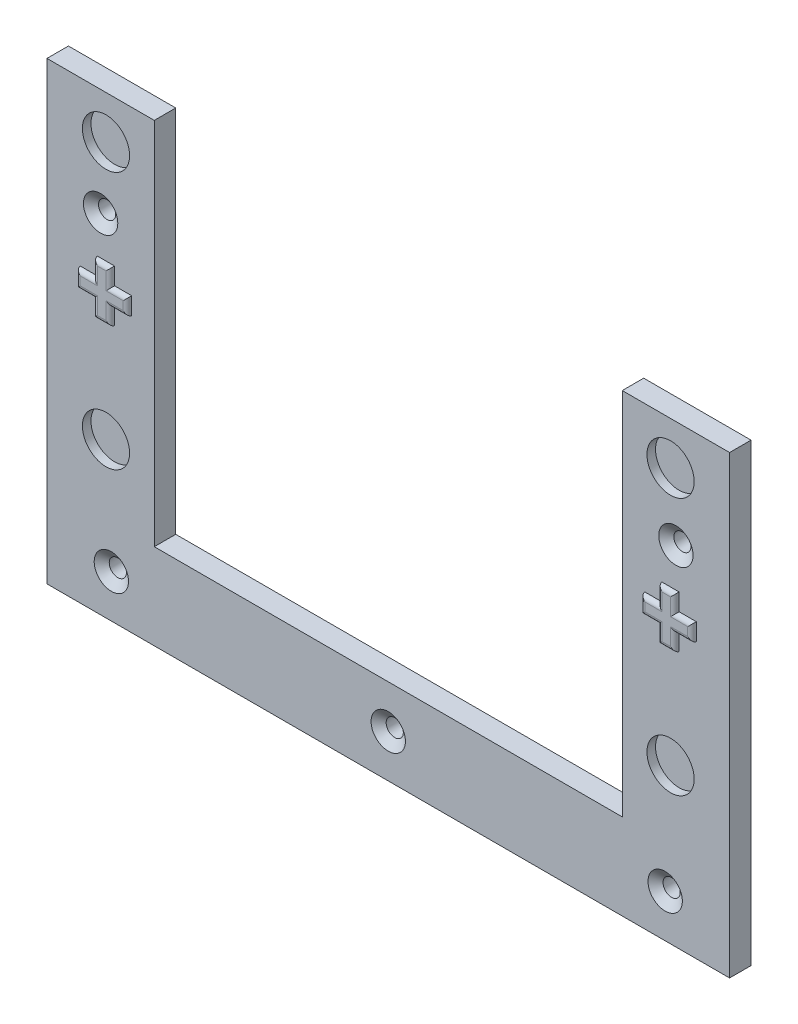
SolidWorks part; units mm, degrees
ref_plane "Plan de face" through (0, 0, 0) normal (0, 0, 1) x (1, 0, 0)
ref_plane "Plan de dessus" through (0, 0, 0) normal (0, 1, 0) x (1, 0, 0)
ref_plane "Plan de droite" through (0, 0, 0) normal (1, 0, 0) x (0, 0, -1)
sketch "Esquisse1" plane through (0, 0, 0) normal (0, 0, 1) x (1, 0, 0)
  line L1 (0, 0) -> (159, 0)
  line L2 (0, 0) -> (0, 106)
  line L3 (0, 106) -> (159, 106)
  line L4 (159, 0) -> (159, 106)
  dimension "D1" = 159
  dimension "D2" = 106
extrude "Boss.-Extru.1" add sketch "Esquisse1" along normal blind 5
sketch "Esquisse2" plane through (0, 0, 0) normal (0, 0, -1) x (-1, 0, 0)
  line L0 (-11.75, 64) -> (-7.75, 64)
  line L1 (-7.75, 64) -> (-7.75, 68)
  line L2 (-19.75, 64) -> (-19.75, 68)
  line L3 (-7.75, 68) -> (-11.75, 68)
  line L4 (-143.25, 64) -> (-139.25, 64)
  line L5 (-79.5, 174.4354) -> (-79.5, -40.1682) construction
  line L6 (-143.25, 68) -> (-139.25, 68)
  line L7 (-143.25, 60) -> (-143.25, 64)
  line L8 (-147.25, 60) -> (-143.25, 60)
  line L9 (-147.25, 64) -> (-147.25, 60)
  line L10 (-143.25, 72) -> (-143.25, 68)
  line L11 (-147.25, 72) -> (-143.25, 72)
  line L12 (-11.75, 68) -> (-11.75, 72)
  line L13 (-11.75, 72) -> (-15.75, 72)
  line L14 (-15.75, 72) -> (-15.75, 68)
  line L15 (-11.75, 64) -> (-11.75, 60)
  line L16 (-11.75, 60) -> (-15.75, 60)
  line L17 (-15.75, 60) -> (-15.75, 64)
  line L18 (-15.75, 68) -> (-19.75, 68)
  line L19 (-15.75, 64) -> (-19.75, 64)
  line L20 (0, 106) -> (0, 0) construction
  line L21 (-159, 0) -> (-159, 106) construction
  line L22 (-147.25, 68) -> (-147.25, 72)
  line L23 (-151.25, 68) -> (-147.25, 68)
  line L24 (-139.25, 64) -> (-139.25, 68)
  line L25 (-151.25, 64) -> (-151.25, 68)
  line L26 (-147.25, 64) -> (-151.25, 64)
  line L28 (-13.75, -9.0235) -> (-13.75, 167.0736) construction
  line L29 (-3.2909, 66) -> (-22.7152, 66) construction
  line L30 (0, 0) -> (-159, 0) construction
  dimension "D3" = 4
  dimension "D4" = 4
  dimension "D5" = 13.75
  dimension "D6" = 66
  dimension "D7" = 2
  dimension "D8" = 4
  dimension "D9" = 4
  dimension "D10" = 4
  dimension "D11" = 4
  dimension "D12" = 4
  dimension "D13" = 4
  dimension "D14" = 79.5
  dimension "D15" = 79.5
  dimension "D16" = 4
  dimension "D17" = 4
  dimension "D18" = 2
  dimension "D19" = 2
  dimension "D25" = 176.0971
sketch "Esquisse3" plane through (0, 0, 0) normal (0, 0, -1) x (-1, 0, 0)
  line L1 (0, 106) -> (0, 0) construction
  line L2 (-159, 0) -> (-159, 106) construction
  line L6 (-159, 0) -> (-159, 106) construction
  line L8 (0, 0) -> (-159, 0) construction
  line L9 (0, 106) -> (0, 0) construction
  circle A0 centre (-13.75, 36) radius 5.5
  circle A1 centre (-13.75, 96) radius 5.5
  circle A2 centre (-145.25, 36) radius 5.5
  circle A3 centre (-145.25, 96) radius 5.5
  dimension "D3" = 11
  dimension "D4" = 11
  dimension "D9" = 11
  dimension "D10" = 11
  dimension "D7" = 13.75
  dimension "D2" = 13.75
  dimension "D5" = 60
  dimension "D6" = 13.75
  dimension "D8" = 13.75
  dimension "D11" = 36
  dimension "D12" = 60
  dimension "D14" = 36
extrude "Enlèv. mat.-Extru.2" cut sketch "Esquisse3" against normal blind 2.2 from offset 3 offset against normal yes
sketch "Esquisse4" plane through (0, 0, 5) normal (0, 0, 1) x (1, 0, 0)
  line L0 (159, 106) -> (0, 106) construction
  line L1 (25, 106) -> (134, 106)
  line L2 (25, 106) -> (25, 20)
  line L3 (25, 20) -> (134, 20)
  line L4 (134, 106) -> (134, 20)
  line L5 (0, 106) -> (0, 0) construction
  line L6 (159, 0) -> (159, 106) construction
  line L7 (0, 0) -> (159, 0) construction
  dimension "D1" = 25
  dimension "D2" = 25
  dimension "D3" = 20
extrude "Enlèv. mat.-Extru.3" cut sketch "Esquisse4" against normal blind 6
sketch "Esquisse5" plane through (0, 0, 5) normal (0, 0, 1) x (1, 0, 0)
  line L0 (0, 0) -> (159, 0) construction
  line L1 (0, 106) -> (0, 0) construction
  line L2 (159, 0) -> (159, 106) construction
  line L3 (159, 106) -> (134, 106) construction
  line L4 (159, 0) -> (159, 106) construction
  line L5 (0, 106) -> (0, 0) construction
  line L6 (25, 106) -> (0, 106) construction
  circle A0 centre (15, 10) radius 2
  circle A1 centre (144, 10) radius 2
  circle A2 centre (12.5, 81) radius 2
  circle A3 centre (146.5, 81) radius 2
  circle A4 centre (79.5, 10) radius 2
  dimension "D1" = 4
  dimension "D2" = 4
  dimension "D7" = 4
  dimension "D8" = 4
  dimension "D13" = 4
  dimension "D3" = 10
  dimension "D4" = 15
  dimension "D5" = 15
  dimension "D6" = 10
  dimension "D9" = 25
  dimension "D10" = 12.5
  dimension "D11" = 12.5
  dimension "D12" = 25
  dimension "D14" = 10
  dimension "D15" = 79.5
  dimension "D16" = 79.5
extrude "Enlèv. mat.-Extru.4" cut sketch "Esquisse5" against normal blind 6
chamfer "Chanfrein1" distance 2 angle 37 5 edges at (148.5, 81, 5) (146, 10, 5) (17, 10, 5) (14.5, 81, 5) (81.5, 10, 5) first distance on face at (81.5, 10, 5)
extrude "Boss.-Extru.2" add sketch "Esquisse2" against normal blind 1 from offset 5 offset against normal yes
fillet "Congé2" radius 1 24 edges at (11.75, 62, 6) (13.75, 60, 6) (15.75, 62, 6) (19.75, 66, 6) (17.75, 64, 6) (17.75, 68, 6) (15.75, 70, 6) (13.75, 72, 6) (11.75, 70, 6) (143.25, 70, 6) (145.25, 72, 6) (147.25, 70, 6) (149.25, 68, 6) (151.25, 66, 6) (149.25, 64, 6) (147.25, 62, 6) (145.25, 60, 6) (143.25, 62, 6) (141.25, 64, 6) (141.25, 68, 6) (139.25, 66, 6) (9.75, 68, 6) (7.75, 66, 6) (9.75, 64, 6)
